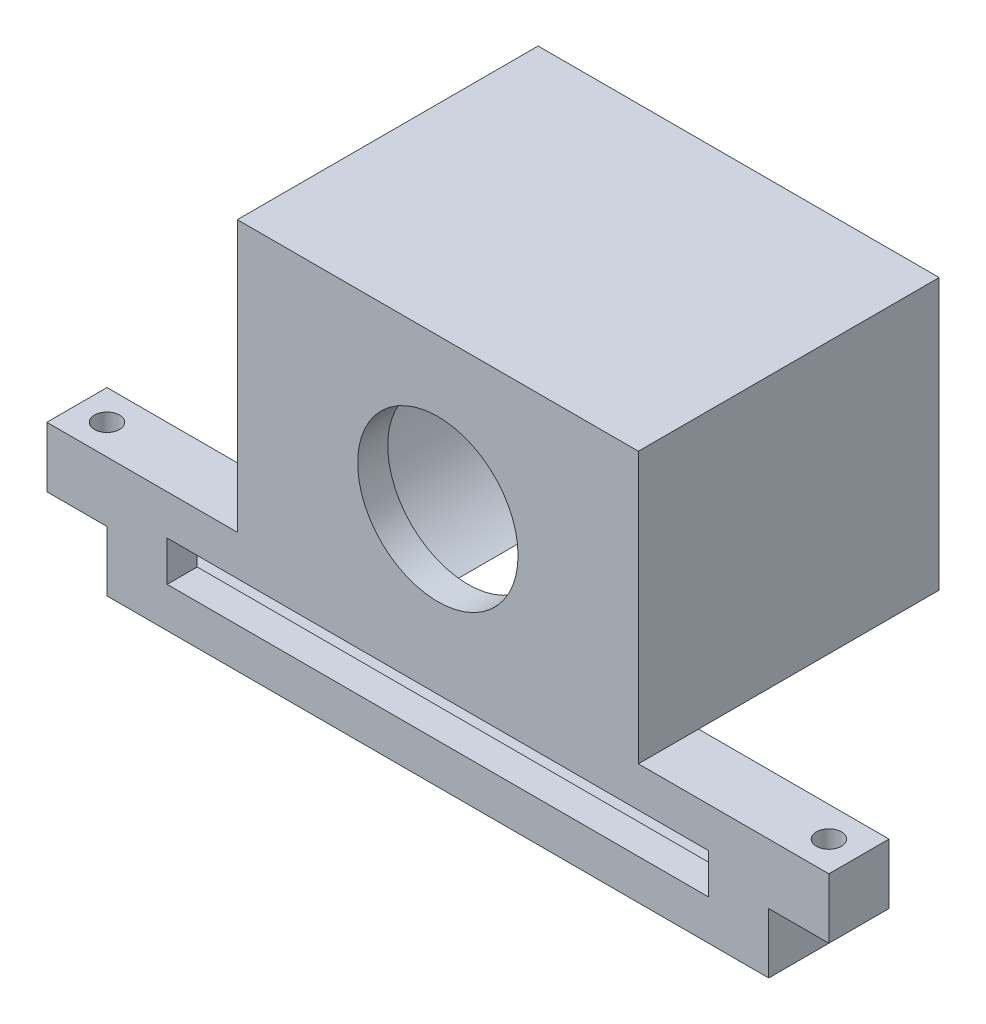
SolidWorks part; units mm, degrees
material "1060 Alloy"
ref_plane "Front Plane" through (0, 0, 0) normal (0, 0, 1) x (1, 0, 0)
ref_plane "Top Plane" through (0, 0, 0) normal (0, 1, 0) x (1, 0, 0)
ref_plane "Right Plane" through (0, 0, 0) normal (1, 0, 0) x (0, 0, -1)
sketch "Sketch1" plane through (0, 0, 0) normal (0, 0, 1) x (1, 0, 0)
  line L0 (0, 0) -> (6, 0)
  line L1 (6, 0) -> (6, -6)
  line L2 (6, -6) -> (72, -6)
  line L3 (72, -6) -> (72, 0)
  line L4 (72, 0) -> (78, 0)
  line L5 (78, 0) -> (78, 6)
  line L6 (78, 6) -> (59, 6)
  line L7 (59, 6) -> (59, 33)
  line L8 (59, 33) -> (19, 33)
  line L9 (19, 33) -> (19, 6)
  line L10 (19, 6) -> (0, 6)
  line L11 (0, 6) -> (0, 0)
  line L13 (12, 2) -> (66, 2)
  line L14 (12, 2) -> (12, -2)
  line L15 (12, -2) -> (66, -2)
  line L16 (66, 2) -> (66, -2)
  circle A0 centre (39, 18) radius 8
  dimension "D12" = 16
  dimension "D1" = 4
  dimension "D2" = 33
  dimension "D3" = 40
  dimension "D4" = 4
  dimension "D5" = 2
  dimension "D6" = 4
  dimension "D7" = 6
  dimension "D8" = 6
  dimension "D9" = 6
  dimension "D10" = 54
  dimension "D11" = 18
  dimension "D13" = 20
extrude "Boss-Extrude1" add sketch "Sketch1" along normal blind 30
sketch "Sketch3" plane through (0, 0, 0) normal (0, 0, -1) x (-1, 0, 0)
  circle A0 centre (-39, 18) radius 13
  dimension "D1" = 26
extrude "Cut-Extrude2" cut sketch "Sketch3" against normal offset from surface (27 mm away) 3 up to face at (39, 0, 30)
hole_wizard "Tap Drill for M3 Tap1" positions "Sketch5" profile "Sketch4" hole size "M3" standard "ISO"
sketch "Sketch5" plane through (53.9899, 0, -7.4052) normal (0, -1, 0) x (-1, 0, 0)
  line L4 (-24.0101, -37.4052) -> (-24.0101, -7.4052) construction
  line L5 (53.9899, -37.4052) -> (53.9899, -7.4052) construction
  line L7 (-18.0101, -37.4052) -> (-24.0101, -37.4052) construction
  point P0 (50.9899, -34.4052)
  point P2 (-21.0101, -34.4052)
  dimension "D1" = 3
  dimension "D2" = 3
  dimension "D3" = 3
sketch "Sketch4" plane through (3, 0, 27) normal (1, 0, 0) x (0, 0, -1)
  line L0 (0, 0) -> (0, 8.7511)
  line L1 (0, 8.7511) -> (1.25, 8)
  line L2 (1.25, 8) -> (1.25, 0)
  line L5 (1.25, 0) -> (0, 0)
  line L10 (0, 8.7511) -> (-1.25, 8) construction
  line L11 (0, -6.35) -> (0, 107.95) construction
  dimension "Hole Dia." = 2.5
  dimension "Hole Depth" = 8
  dimension "Drill Angle" = 118
sketch "Sketch6" plane through (0, 0, 0) normal (0, 0, -1) x (-1, 0, 0)
  line L2 (-78, 6) -> (0, 6)
  line L3 (-78, 6) -> (-78, -6)
  line L4 (-78, -6) -> (0, -6)
  line L5 (0, 6) -> (0, -6)
extrude "Cut-Extrude3" cut sketch "Sketch6" against normal offset from surface (24 mm away) 6 up to face at (39, 0, 30)
sketch "Sketch7" plane through (0, 0, 24) normal (0, 0, -1) x (-1, 0, 0)
  line L0 (-66, 2) -> (-66, -2) construction
  line L1 (-68, 3) -> (-10, 3)
  line L2 (-68, 3) -> (-68, -3)
  line L3 (-68, -3) -> (-10, -3)
  line L4 (-10, 3) -> (-10, -3)
  line L5 (-12, 2) -> (-66, 2) construction
  line L6 (-66, -2) -> (-12, -2) construction
  line L7 (-12, -2) -> (-12, 2) construction
  dimension "D1" = 2
  dimension "D2" = 1
  dimension "D3" = 1
  dimension "D4" = 2
extrude "Cut-Extrude4" cut sketch "Sketch7" against normal blind 3
